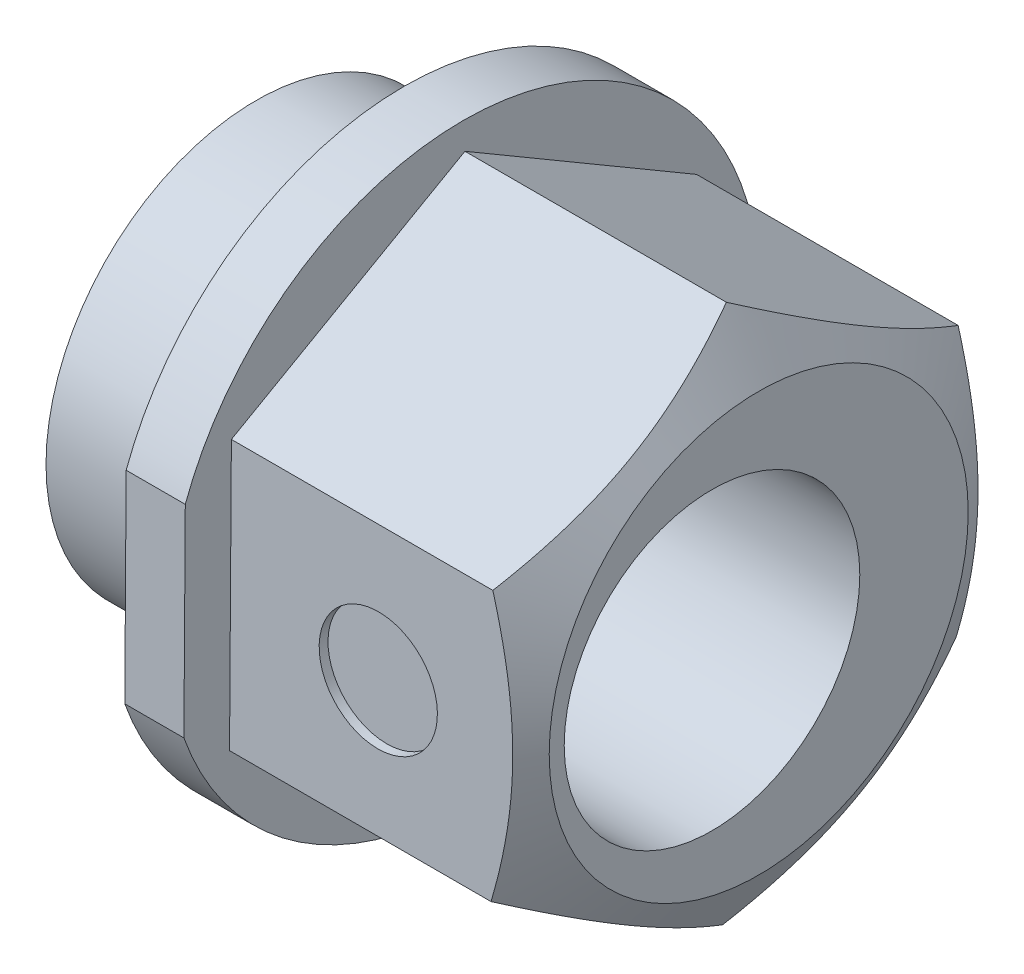
SolidWorks part; units mm, degrees
material "Chrome Stainless Steel"
ref_plane "Front Plane" through (0, 0, 0) normal (0, 0, 1) x (1, 0, 0)
ref_plane "Top Plane" through (0, 0, 0) normal (0, 1, 0) x (1, 0, 0)
ref_plane "Right Plane" through (0, 0, 0) normal (1, 0, 0) x (0, 0, -1)
sketch "Sketch2" plane through (0, 0, 0) normal (1, 0, 0) x (0, 0, -1)
  line L1 (3.9194, -2.2986) -> (3.9504, 2.245)
  line L2 (3.9504, 2.245) -> (0.0309, 4.5436)
  line L3 (0.0309, 4.5436) -> (-3.9194, 2.2986)
  line L4 (-3.9194, 2.2986) -> (-3.9504, -2.245)
  line L5 (-3.9504, -2.245) -> (-0.0309, -4.5436)
  line L6 (-0.0309, -4.5436) -> (3.9194, -2.2986)
  circle A0 centre (0, 0) radius 3.935 construction
  dimension "D1" = 7.87
extrude "Boss-Extrude1" add sketch "Sketch2" along normal blind 5
sketch "Sketch6" plane through (0, 0, 0) normal (-1, 0, 0) x (0, 0, 1)
  line L0 (4.6992, 1.7371) -> (4.7108, 0.0321)
  line L1 (5.7224, -1.6698) -> (5.6992, 1.74) construction
  line L2 (4.7108, 0.0321) -> (4.7224, -1.6729)
  line L3 (4.6992, 1.7371) -> (4.7224, -1.6729) construction
  line L4 (3.9194, 2.2986) -> (3.9504, -2.245) construction
  arc A0 (4.6992, 1.7371) -> (4.7224, -1.6729) centre (0, 0) ccw
  dimension "D1" = 10.02
  dimension "D2" = 3.41
  dimension "D3" = 1
  dimension "D4" = 1
extrude "Boss-Extrude3" add sketch "Sketch6" along normal blind 1
sketch "Sketch4" plane through (-1, 0, 0) normal (-1, 0, 0) x (0, 0, 1)
  circle A0 centre (0, 0) radius 3.555
  dimension "D1" = 7.11
extrude "Boss-Extrude4" add sketch "Sketch4" along normal blind 2.5
sketch "Sketch3" plane through (-3.5, 0, 0) normal (-1, 0, 0) x (0, 0, 1)
  line L0 (0, 0) -> (0.79, 0) construction
  circle A0 centre (0.79, 0) radius 2.5
  dimension "D1" = 5
  dimension "D2" = 0.79
sketch "Sketch5" plane through (0, 0.0268, 3.9349) normal (0, -0.0068, -1) x (1, 0, 0)
  line L1 (5, 0) -> (0, 0) construction
  line L2 (5, -2.2719) -> (5, 2.2719) construction
  line L3 (0, -2.2719) -> (0, 2.2719) construction
  circle A0 centre (2.5, 0) radius 1
  dimension "D1" = 2
extrude "Cut-Extrude3" cut sketch "Sketch5" along normal blind 0.15
extrude "Cut-Extrude5" cut sketch "Sketch3" against normal through all
sketch "Sketch7" plane through (0, 0, 0) normal (0, 0, 1) x (1, 0, 0)
  line L0 (4.4226, 4.5436) -> (5, 3.5436)
  line L1 (9.4226, 8.5436) -> (4.4226, 8.5436)
  line L2 (9.4226, 8.5436) -> (9.4226, 3.5436)
  line L3 (9.4226, 3.5436) -> (5, 3.5436)
  line L4 (4.4226, 8.5436) -> (4.4226, 4.5436)
  line L5 (5, 2.245) -> (5, 4.5436) construction
  line L6 (4.4226, 4.5436) -> (9.4226, 4.5436) construction
  line L7 (5, 4.5436) -> (0, 4.5436) construction
  dimension "D1" = 150
  dimension "D2" = 1
  dimension "D3" = 5
  dimension "D4" = 5
ref_axis "Axis1" through (0, 0, 0) along (1, 0, 0)
revolve "Cut-Revolve1" cut sketch "Sketch7" angle 360 about axis through (0, 0, 0) along (1, 0, 0)
